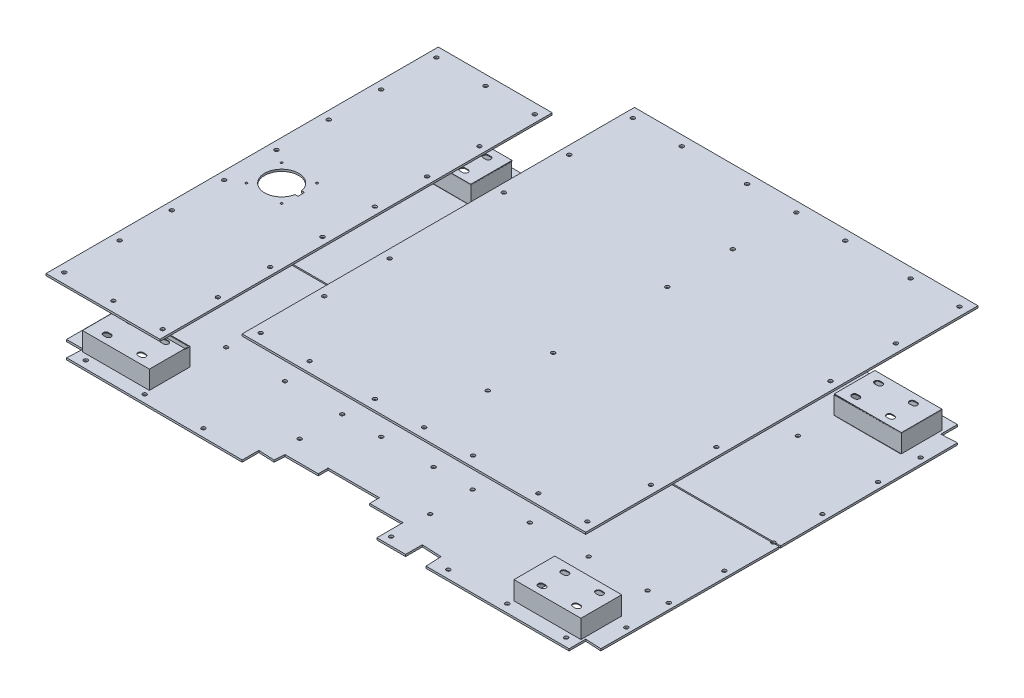
SolidWorks part; units mm, degrees
ref_plane "Front Plane" through (0, 0, 0) normal (0, 0, 1) x (1, 0, 0)
ref_plane "Top Plane" through (0, 0, 0) normal (0, 1, 0) x (1, 0, 0)
ref_plane "Right Plane" through (0, 0, 0) normal (1, 0, 0) x (0, 0, -1)
sketch "Sketch2" plane through (0, 422.0595, 0) normal (0, 1, 0) x (1, 0, 0)
  line L1 (715.0951, -383.2952) -> (690.8951, -384.4952)
  line L2 (690.8951, -384.4952) -> (690.8951, -359.0952)
  line L3 (690.8951, -359.0952) -> (466.2951, -359.0952)
  line L4 (466.2951, -359.0952) -> (465.0951, -383.2952)
  line L5 (465.0951, -383.2952) -> (440.8951, -384.4952)
  line L6 (440.8951, -384.4952) -> (440.8951, -359.0952)
  line L7 (440.8951, -359.0952) -> (390.8951, -359.0952)
  line L8 (390.8951, -359.0952) -> (390.8951, -399.0952)
  line L9 (390.8951, -483.6952) -> (390.8951, -359.0952) construction
  line L10 (390.8951, -399.0952) -> (216.2951, -399.0952)
  line L11 (216.2951, -384.4952) -> (216.2951, -483.6952) construction
  line L12 (216.2951, -399.0952) -> (215.0951, -383.2952)
  line L13 (215.0951, -383.2952) -> (190.8951, -384.4952)
  line L14 (190.8951, -384.4952) -> (190.8951, -359.0952)
  line L15 (190.8951, -359.0952) -> (-84.9049, -360.2952)
  line L16 (-84.9049, -360.2952) -> (-83.7049, -384.4952)
  line L17 (-83.7049, -384.4952) -> (-109.1049, -384.4952)
  line L18 (-109.1049, -384.4952) -> (-109.1049, -933.6952)
  line L19 (-109.1049, -933.6952) -> (-109.1049, -384.4952) construction
  line L20 (715.0951, -383.2952) -> (716.2951, -659.0952)
  line L21 (716.2951, -384.4952) -> (716.2951, -933.6952) construction
  line L22 (716.2951, -659.0952) -> (-109.1049, -659.0952) construction
  line L23 (715.0951, -934.8952) -> (716.2951, -659.0952)
  line L24 (-83.7049, -933.6952) -> (-109.1049, -933.6952)
  line L25 (-84.9049, -957.8952) -> (-83.7049, -933.6952)
  line L26 (190.8951, -959.0952) -> (-84.9049, -957.8952)
  line L27 (190.8951, -933.6952) -> (190.8951, -959.0952)
  line L28 (215.0951, -934.8952) -> (190.8951, -933.6952)
  line L29 (216.2951, -919.0952) -> (215.0951, -934.8952)
  line L30 (390.8951, -919.0952) -> (216.2951, -919.0952)
  line L31 (390.8951, -959.0952) -> (390.8951, -919.0952)
  line L32 (440.8951, -959.0952) -> (390.8951, -959.0952)
  line L33 (440.8951, -933.6952) -> (440.8951, -959.0952)
  line L34 (465.0951, -934.8952) -> (440.8951, -933.6952)
  line L35 (466.2951, -959.0952) -> (465.0951, -934.8952)
  line L36 (690.8951, -959.0952) -> (466.2951, -959.0952)
  line L37 (690.8951, -933.6952) -> (690.8951, -959.0952)
  line L38 (715.0951, -934.8952) -> (690.8951, -933.6952)
  line L39 (712.1088, -386.4469) -> (713.2907, -658.0952)
  line L40 (712.1088, -386.4469) -> (687.8951, -387.6476)
  line L41 (687.8951, -387.6476) -> (687.8951, -362.0952)
  line L42 (687.8951, -362.0952) -> (469.15, -362.0952)
  line L43 (469.15, -362.0952) -> (467.9569, -386.1569)
  line L44 (467.9569, -386.1569) -> (437.8951, -387.6476)
  line L45 (437.8951, -387.6476) -> (437.8951, -362.0952)
  line L46 (437.8951, -362.0952) -> (393.8951, -362.0952)
  line L47 (393.8951, -362.0952) -> (393.8951, -402.0952)
  line L48 (393.8951, -402.0952) -> (213.5143, -402.0952)
  line L49 (213.5143, -402.0952) -> (212.325, -386.4362)
  line L50 (212.325, -386.4362) -> (187.8951, -387.6476)
  line L51 (187.8951, -387.6476) -> (187.8951, -362.1082)
  line L52 (187.8951, -362.1082) -> (-81.7531, -363.2815)
  line L53 (-81.7531, -363.2815) -> (-80.5525, -387.4952)
  line L54 (-80.5525, -387.4952) -> (-106.1049, -387.4952)
  line L55 (-106.1049, -387.4952) -> (-106.1049, -658.0952)
  line L56 (-80.5525, -930.6952) -> (-106.1049, -930.6952)
  line L57 (-81.7531, -954.9089) -> (-80.5525, -930.6952)
  line L58 (187.8951, -956.0821) -> (-81.7531, -954.9089)
  line L59 (187.8951, -930.5427) -> (187.8951, -956.0821)
  line L60 (212.325, -931.7541) -> (187.8951, -930.5427)
  line L61 (213.5143, -916.0952) -> (212.325, -931.7541)
  line L62 (393.8951, -916.0952) -> (213.5143, -916.0952)
  line L63 (393.8951, -956.0952) -> (393.8951, -916.0952)
  line L64 (437.8951, -956.0952) -> (393.8951, -956.0952)
  line L65 (437.8951, -930.5427) -> (437.8951, -956.0952)
  line L66 (467.9569, -932.0334) -> (437.8951, -930.5427)
  line L67 (469.15, -956.0952) -> (467.9569, -932.0334)
  line L68 (687.8951, -956.0952) -> (469.15, -956.0952)
  line L69 (687.8951, -930.5427) -> (687.8951, -956.0952)
  line L70 (712.1088, -931.7434) -> (687.8951, -930.5427)
  line L71 (712.1088, -931.7434) -> (713.2907, -660.0952)
  line L72 (716.2951, -658.0952) -> (716.2907, -658.0952)
  line L73 (716.2951, -660.0952) -> (716.2907, -660.0952)
  line L74 (713.2907, -660.0952) -> (-106.1049, -660.0952)
  line L75 (713.2907, -658.0952) -> (-106.1049, -658.0952)
  line L76 (716.2951, -660.0952) -> (-109.1049, -660.0952) construction
  line L77 (-106.1049, -660.0952) -> (-106.1049, -930.6952)
  line L78 (716.2951, -658.0952) -> (-109.1049, -658.0952) construction
  line L80 (-106.1049, -387.4952) -> (-106.1049, -930.6952) construction
  line L81 (712.1088, -386.4469) -> (713.2951, -659.0952) construction
  line L82 (712.1088, -931.7434) -> (713.2951, -659.0952) construction
  circle A0 centre (-96.2049, -884.0952) radius 3 construction
  circle A1 centre (116.2951, -819.0952) radius 3 construction
  circle A2 centre (-63.7049, -819.0952) radius 3 construction
  circle A3 centre (-96.2049, -819.0952) radius 3 construction
  circle A4 centre (-96.2049, -884.0952) radius 3
  circle A5 centre (116.2951, -819.0952) radius 3
  circle A6 centre (-63.7049, -819.0952) radius 3
  circle A7 centre (-96.2049, -819.0952) radius 3
  circle A8 centre (-96.2049, -734.0952) radius 3 construction
  circle A9 centre (-96.2049, -734.0952) radius 3
  circle A10 centre (116.2951, -943.6952) radius 3 construction
  circle A11 centre (26.2951, -943.6952) radius 3 construction
  circle A12 centre (-63.7049, -943.6952) radius 3 construction
  circle A13 centre (116.2951, -943.6952) radius 3
  circle A14 centre (26.2951, -943.6952) radius 3
  circle A15 centre (-63.7049, -943.6952) radius 3
  circle A16 centre (-96.2049, -659.0952) radius 3 construction
  circle A17 centre (-96.2049, -659.0952) radius 3
  circle A18 centre (26.2951, -819.0952) radius 3 construction
  circle A19 centre (26.2951, -819.0952) radius 3
  circle A20 centre (343.5951, -819.0952) radius 3 construction
  circle A21 centre (203.7951, -734.0952) radius 3 construction
  circle A22 centre (263.5951, -819.0952) radius 3 construction
  circle A23 centre (203.7951, -819.0952) radius 3 construction
  circle A24 centre (203.7951, -884.0952) radius 3 construction
  circle A25 centre (343.5951, -819.0952) radius 3
  circle A26 centre (203.7951, -734.0952) radius 3
  circle A27 centre (263.5951, -819.0952) radius 3
  circle A28 centre (203.7951, -819.0952) radius 3
  circle A29 centre (203.7951, -884.0952) radius 3
  circle A30 centre (203.7951, -659.0952) radius 3 construction
  circle A31 centre (203.7951, -659.0952) radius 3
  circle A32 centre (26.2951, -499.0952) radius 3 construction
  circle A33 centre (26.2951, -499.0952) radius 3
  circle A34 centre (116.2951, -499.0952) radius 3 construction
  circle A35 centre (116.2951, -499.0952) radius 3
  circle A36 centre (203.7951, -499.0952) radius 3 construction
  circle A37 centre (203.7951, -499.0952) radius 3
  circle A38 centre (203.7951, -434.0952) radius 3 construction
  circle A39 centre (203.7951, -434.0952) radius 3
  circle A40 centre (116.2951, -374.4952) radius 3 construction
  circle A41 centre (116.2951, -374.4952) radius 3
  circle A42 centre (26.2951, -374.4952) radius 3 construction
  circle A43 centre (26.2951, -374.4952) radius 3
  circle A44 centre (-63.7049, -374.4952) radius 3 construction
  circle A45 centre (-63.7049, -374.4952) radius 3
  circle A46 centre (-96.2049, -434.0952) radius 3 construction
  circle A47 centre (-96.2049, -499.0952) radius 3 construction
  circle A48 centre (-96.2049, -584.0952) radius 3 construction
  circle A49 centre (-96.2049, -434.0952) radius 3
  circle A50 centre (-96.2049, -499.0952) radius 3
  circle A51 centre (-96.2049, -584.0952) radius 3
  circle A52 centre (-63.7049, -499.0952) radius 3 construction
  circle A53 centre (-63.7049, -499.0952) radius 3
  circle A54 centre (203.7951, -584.0952) radius 3 construction
  circle A55 centre (203.7951, -584.0952) radius 3
  circle A56 centre (403.3951, -584.0952) radius 3 construction
  circle A57 centre (403.3951, -584.0952) radius 3
  circle A58 centre (490.8951, -499.0952) radius 3 construction
  circle A59 centre (490.8951, -499.0952) radius 3
  circle A60 centre (580.8951, -499.0952) radius 3 construction
  circle A61 centre (580.8951, -499.0952) radius 3
  circle A62 centre (490.8951, -374.4952) radius 3 construction
  circle A63 centre (490.8951, -374.4952) radius 3
  circle A64 centre (580.8951, -374.4952) radius 3 construction
  circle A65 centre (580.8951, -374.4952) radius 3
  circle A66 centre (703.3951, -584.0952) radius 3 construction
  circle A67 centre (703.3951, -499.0952) radius 3 construction
  circle A68 centre (703.3951, -434.0952) radius 3 construction
  circle A69 centre (670.8951, -374.4952) radius 3 construction
  circle A70 centre (703.3951, -584.0952) radius 3
  circle A71 centre (703.3951, -499.0952) radius 3
  circle A72 centre (703.3951, -434.0952) radius 3
  circle A73 centre (670.8951, -374.4952) radius 3
  circle A74 centre (703.3951, -884.0952) radius 3 construction
  circle A75 centre (703.3951, -819.0952) radius 3 construction
  circle A76 centre (703.3951, -734.0952) radius 3 construction
  circle A77 centre (703.3951, -659.0952) radius 3 construction
  circle A78 centre (703.3951, -884.0952) radius 3
  circle A79 centre (703.3951, -819.0952) radius 3
  circle A80 centre (703.3951, -734.0952) radius 3
  circle A81 centre (703.3951, -659.0952) radius 3
  circle A82 centre (490.8951, -943.6952) radius 3 construction
  circle A83 centre (580.8951, -943.6952) radius 3 construction
  circle A84 centre (670.8951, -943.6952) radius 3 construction
  circle A85 centre (490.8951, -943.6952) radius 3
  circle A86 centre (580.8951, -943.6952) radius 3
  circle A87 centre (670.8951, -943.6952) radius 3
  circle A89 centre (580.8951, -819.0952) radius 3 construction
  circle A90 centre (670.8951, -819.0952) radius 3 construction
  circle A91 centre (580.8951, -819.0952) radius 3
  circle A92 centre (670.8951, -819.0952) radius 3
  circle A93 centre (490.8951, -819.0952) radius 3 construction
  circle A94 centre (490.8951, -819.0952) radius 3
  circle A95 centre (403.3951, -943.6952) radius 3 construction
  circle A96 centre (403.3951, -884.0952) radius 3 construction
  circle A97 centre (403.3951, -819.0952) radius 3 construction
  circle A98 centre (403.3951, -734.0952) radius 3 construction
  circle A99 centre (403.3951, -943.6952) radius 3
  circle A100 centre (403.3951, -884.0952) radius 3
  circle A101 centre (403.3951, -819.0952) radius 3
  circle A102 centre (403.3951, -734.0952) radius 3
  circle A103 centre (403.3951, -659.0952) radius 3 construction
  circle A104 centre (403.3951, -499.0952) radius 3 construction
  circle A105 centre (403.3951, -434.0952) radius 3 construction
  circle A106 centre (403.3951, -374.4952) radius 3 construction
  circle A107 centre (403.3951, -659.0952) radius 3
  circle A108 centre (403.3951, -499.0952) radius 3
  circle A109 centre (403.3951, -434.0952) radius 3
  circle A110 centre (403.3951, -374.4952) radius 3
  circle A111 centre (343.5951, -499.0952) radius 3 construction
  circle A113 centre (263.5951, -499.0952) radius 3 construction
  circle A114 centre (343.5951, -499.0952) radius 3
  circle A115 centre (263.5951, -499.0952) radius 3
  dimension "D1" = 40
  dimension "D2" = 3
  dimension "D3" = 1
  dimension "D4" = 1
extrude "Boss-Extrude1" add sketch "Sketch2" along normal blind 3 contours A107 L75 A81 L39 L40 L41 L42 L43 L44 L45 L46 L47 L48 L49 L50 L51 L52 L53 L54 L55 A17 A31 A115 A114 A110 A109 A108 A73 A72 A71 A70 A65 A63 A61 | A107 L74 A31 A17 L77 L56 L57 L58 L59 L60 L61 L62 L63 L64 L65 L66 L67 L68 L69 L70 L71 A81 A102 A101 A100 A99 A94 A92 A91 A87 A86 A85 A80 A79 region at (303.342, 422.0595, 515.8841) region at (303.2971, 422.0595, 802.3042)
sketch "Sketch4" plane through (0, 592.0595, 0) normal (0, 1, 0) x (1, 0, 0)
  line L0 (716.2951, -359.0952) -> (190.8951, -359.0952) construction
  line L1 (190.8951, -359.0952) -> (190.8951, -959.0952) construction
  line L2 (190.8951, -933.6952) -> (190.8951, -384.4952) construction
  line L3 (716.2951, -959.0952) -> (716.2951, -359.0952) construction
  line L4 (190.8951, -959.0952) -> (716.2951, -959.0952) construction
  line L5 (716.2951, -359.0952) -> (190.8951, -359.0952)
  line L6 (190.8951, -359.0952) -> (190.8951, -959.0952)
  line L7 (190.8951, -933.6952) -> (190.8951, -384.4952)
  line L8 (716.2951, -959.0952) -> (716.2951, -359.0952)
  line L9 (190.8951, -959.0952) -> (716.2951, -959.0952)
  line L10 (190.8951, -359.0952) -> (716.2951, -959.0952) construction
  line L11 (190.8951, -959.0952) -> (716.2951, -359.0952) construction
  line L12 (453.5951, -659.0952) -> (716.2951, -659.0952) construction
  circle A1 centre (628.5951, -943.6952) radius 3 construction
  circle A2 centre (703.3951, -943.6952) radius 3 construction
  circle A3 centre (528.5951, -943.6952) radius 3 construction
  circle A4 centre (703.3951, -846.3952) radius 3 construction
  circle A5 centre (703.3951, -746.3952) radius 3 construction
  circle A6 centre (453.7951, -943.6952) radius 3 construction
  circle A7 centre (453.7951, -846.3952) radius 3 construction
  circle A8 centre (378.5951, -943.6952) radius 3 construction
  circle A9 centre (278.5951, -943.6952) radius 3 construction
  circle A10 centre (203.7951, -943.6952) radius 3 construction
  circle A11 centre (203.7951, -746.3952) radius 3 construction
  circle A12 centre (203.7951, -846.3952) radius 3 construction
  circle A13 centre (453.7951, -746.3952) radius 3 construction
  circle A14 centre (453.7951, -746.3952) radius 3
  circle A15 centre (203.7951, -846.3952) radius 3
  circle A16 centre (203.7951, -746.3952) radius 3
  circle A17 centre (203.7951, -943.6952) radius 3
  circle A18 centre (278.5951, -943.6952) radius 3
  circle A19 centre (378.5951, -943.6952) radius 3
  circle A20 centre (453.7951, -846.3952) radius 3
  circle A21 centre (453.7951, -943.6952) radius 3
  circle A22 centre (703.3951, -746.3952) radius 3
  circle A23 centre (703.3951, -846.3952) radius 3
  circle A24 centre (528.5951, -943.6952) radius 3
  circle A25 centre (703.3951, -943.6952) radius 3
  circle A26 centre (628.5951, -943.6952) radius 3
  circle A40 centre (628.5951, -374.4952) radius 3
  circle A41 centre (703.3951, -374.4952) radius 3
  circle A42 centre (528.5951, -374.4952) radius 3
  circle A43 centre (703.3951, -471.7952) radius 3
  circle A44 centre (703.3951, -571.7952) radius 3
  circle A45 centre (453.7951, -374.4952) radius 3
  circle A46 centre (453.7951, -471.7952) radius 3
  circle A47 centre (378.5951, -374.4952) radius 3
  circle A48 centre (278.5951, -374.4952) radius 3
  circle A49 centre (203.7951, -374.4952) radius 3
  circle A50 centre (203.7951, -571.7952) radius 3
  circle A51 centre (203.7951, -471.7952) radius 3
  circle A52 centre (453.7951, -571.7952) radius 3
extrude "Boss-Extrude2" add sketch "Sketch4" along normal blind 3 separate body contours L5 L6 L9 L8 | A49 | A48 | A47 | A46 | A51 | A50 | A52 | A45 | A42 | A40 | A41 | A43 | A44 | A22 | A14 | A16 | A15 | A18 | A19 | A20 | A21 | A24 | A26 | A23 | A25 | A17
sketch "Sketch6" plane through (0, 522.0595, 0) normal (0, 1, 0) x (1, 0, 0)
  line L0 (-109.1049, -959.0952) -> (-109.1049, -359.0952) construction
  line L1 (65.0951, -384.4952) -> (65.0951, -933.6952) construction
  line L2 (-109.1049, -959.0952) -> (-109.1049, -359.0952)
  line L3 (65.0951, -384.4952) -> (65.0951, -933.6952)
  line L4 (65.0951, -933.6952) -> (65.0951, -959.0952)
  line L5 (190.8951, -959.0952) -> (-109.1049, -959.0952) construction
  line L6 (65.0951, -959.0952) -> (-109.1049, -959.0952)
  line L7 (65.0951, -384.4952) -> (65.0951, -359.0952)
  line L8 (190.8951, -359.0952) -> (-109.1049, -359.0952) construction
  line L9 (65.0951, -359.0952) -> (-109.1049, -359.0952)
  line L10 (65.0951, -659.0952) -> (-109.1049, -659.0952) construction
  circle A0 centre (-96.6049, -943.6952) radius 3 construction
  circle A1 centre (-21.3999, -943.6952) radius 3 construction
  circle A2 centre (53.7951, -943.6952) radius 3 construction
  circle A3 centre (-96.6049, -943.6952) radius 3
  circle A4 centre (-21.3999, -943.6952) radius 3
  circle A5 centre (53.7951, -943.6952) radius 3
  circle A6 centre (-96.6049, -859.0952) radius 3 construction
  circle A7 centre (53.7951, -859.0952) radius 3 construction
  circle A8 centre (-96.6049, -859.0952) radius 3
  circle A9 centre (53.7951, -859.0952) radius 3
  circle A10 centre (53.7951, -699.0952) radius 3 construction
  circle A11 centre (-96.6049, -699.0952) radius 3 construction
  circle A12 centre (53.7951, -779.0952) radius 3 construction
  circle A13 centre (-96.6049, -779.0952) radius 3 construction
  circle A14 centre (53.7951, -699.0952) radius 3
  circle A15 centre (-96.6049, -699.0952) radius 3
  circle A16 centre (53.7951, -779.0952) radius 3
  circle A17 centre (-96.6049, -779.0952) radius 3
  circle A27 centre (-96.6049, -619.0952) radius 3
  circle A28 centre (-96.6049, -539.0952) radius 3
  circle A29 centre (53.7951, -539.0952) radius 3
  circle A30 centre (53.7951, -619.0952) radius 3
  circle A31 centre (53.7951, -459.0952) radius 3
  circle A32 centre (-96.6049, -459.0952) radius 3
  circle A33 centre (53.7951, -374.4952) radius 3
  circle A34 centre (-21.3999, -374.4952) radius 3
  circle A35 centre (-96.6049, -374.4952) radius 3
extrude "Boss-Extrude3" add sketch "Sketch6" along normal blind 3 separate body
sketch "Sketch9" plane through (0, 525.0595, 0) normal (0, 1, 0) x (1, 0, 0)
  line L0 (-48.7049, -659.0952) -> (-22.7049, -659.0952) construction
  line L1 (-48.7049, -654.0952) -> (-22.7049, -654.0952) construction
  line L2 (-48.7049, -664.0952) -> (-22.7049, -664.0952) construction
  line L3 (-23.1902, -654.0952) -> (-18.6902, -654.0952)
  line L4 (-18.6902, -654.0952) -> (-18.6902, -664.0952)
  line L5 (-18.6902, -664.0952) -> (-23.1902, -664.0952)
  arc A0 (-23.1902, -654.0952) -> (-23.1902, -664.0952) centre (-48.7049, -659.0952) ccw
  dimension "D1" = 52
  dimension "D4" = 4.5
  dimension "D2" = 5
  dimension "D3" = 5
extrude "Cut-Extrude1" cut sketch "Sketch9" against normal up to next (3 mm away)
sketch "Sketch10" plane through (0, 525.0595, 0) normal (0, 1, 0) x (1, 0, 0)
  circle A0 centre (-21.7049, -632.0952) radius 1.6
  circle A1 centre (-21.7049, -686.0952) radius 1.6
  circle A2 centre (-75.7049, -632.0952) radius 1.6
  circle A3 centre (-75.7049, -686.0952) radius 1.6
  dimension "D1" = 3.2
  dimension "D2" = 3.2
  dimension "D3" = 3.2
  dimension "D4" = 3.2
extrude "Cut-Extrude4" cut sketch "Sketch10" against normal up to next (3 mm away)
sketch "Sketch11" plane through (0, 422.0595, 0) normal (0, -1, 0) x (1, 0, 0)
  line L0 (264.2951, 916.0952) -> (264.2951, 901.0952)
  line L1 (393.8951, 916.0952) -> (213.5143, 916.0952) construction
  line L2 (264.2951, 901.0952) -> (342.8951, 901.0952)
  line L3 (342.8951, 901.0952) -> (342.8951, 916.0952)
  line L4 (264.2951, 402.0952) -> (342.8951, 402.0952)
  line L5 (390.8951, 959.0952) -> (390.8951, 834.4952) construction
  line L6 (216.2951, 959.0952) -> (216.2951, 834.4952) construction
  line L7 (216.2951, 659.0952) -> (416.2951, 659.0952) construction
  line L8 (216.2951, 809.0952) -> (216.2951, 509.0952) construction
  line L9 (416.2951, 809.0952) -> (416.2951, 509.0952) construction
  line L10 (342.8951, 417.0952) -> (342.8951, 402.0952)
  line L11 (264.2951, 417.0952) -> (342.8951, 417.0952)
  line L12 (264.2951, 402.0952) -> (264.2951, 417.0952)
  line L13 (264.2951, 916.0952) -> (342.8951, 916.0952)
  dimension "D1" = 15
  dimension "D2" = 48
  dimension "D3" = 48
extrude "Cut-Extrude5" cut sketch "Sketch11" against normal up to next (3 mm away)
sketch "Sketch13" plane through (0, 422.0595, 0) normal (0, -1, 0) x (1, 0, 0)
  line L1 (683.5951, 933.6952) -> (583.5951, 933.6952)
  line L3 (683.5951, 873.6952) -> (583.5951, 873.6952)
  line L4 (583.5951, 933.6952) -> (583.5951, 873.6952)
  line L7 (303.5951, 901.0952) -> (303.5951, 417.0952) construction
  line L22 (683.5951, 933.6952) -> (683.5951, 873.6952)
  line L24 (264.2951, 901.0952) -> (342.8951, 901.0952) construction
  line L25 (342.8951, 417.0952) -> (264.2951, 417.0952) construction
  line L26 (303.5951, 659.0952) -> (712.9729, 659.0952) construction
  line L29 (687.8951, 956.0952) -> (469.15, 956.0952) construction
  line L30 (683.5951, 384.4952) -> (683.5951, 444.4952)
  line L31 (583.5951, 384.4952) -> (583.5951, 444.4952)
  line L32 (683.5951, 444.4952) -> (583.5951, 444.4952)
  line L33 (683.5951, 384.4952) -> (583.5951, 384.4952)
  line L34 (-76.4049, 933.6952) -> (-76.4049, 873.6952)
  line L35 (23.5951, 933.6952) -> (23.5951, 873.6952)
  line L36 (-76.4049, 873.6952) -> (23.5951, 873.6952)
  line L37 (-76.4049, 933.6952) -> (23.5951, 933.6952)
  line L38 (-76.4049, 384.4952) -> (23.5951, 384.4952)
  line L39 (-76.4049, 444.4952) -> (23.5951, 444.4952)
  line L40 (23.5951, 384.4952) -> (23.5951, 444.4952)
  line L41 (-76.4049, 384.4952) -> (-76.4049, 444.4952)
  dimension "D1" = 60
  dimension "D2" = 100
  dimension "D3" = 22.4
  dimension "D4" = 380
extrude "Cut-Extrude6" cut sketch "Sketch13" against normal up to next (3 mm away)
sketch "Sketch15" plane through (0, 422.0595, 0) normal (0, -1, 0) x (1, 0, 0)
  line L0 (583.5951, 933.6952) -> (583.5951, 873.6952) construction
  line L1 (583.5951, 873.6952) -> (683.5951, 873.6952) construction
  line L2 (683.5951, 933.6952) -> (583.5951, 933.6952) construction
  line L3 (683.5951, 873.6952) -> (683.5951, 933.6952) construction
  line L4 (583.5951, 933.6952) -> (583.5951, 873.6952)
  line L5 (583.5951, 873.6952) -> (683.5951, 873.6952)
  line L6 (683.5951, 933.6952) -> (583.5951, 933.6952)
  line L7 (683.5951, 873.6952) -> (683.5951, 933.6952)
  line L8 (582.3951, 934.8952) -> (582.3951, 872.4952)
  line L9 (582.3951, 872.4952) -> (684.7951, 872.4952)
  line L10 (684.7951, 872.4952) -> (684.7951, 934.8952)
  line L11 (684.7951, 934.8952) -> (582.3951, 934.8952)
  line L13 (303.5951, 901.0952) -> (303.5951, 416.7343) construction
  line L14 (264.2951, 901.0952) -> (342.8951, 901.0952) construction
  line L15 (303.5951, 658.9147) -> (713.2907, 658.0952) construction
  line L16 (683.6879, 381.4114) -> (581.2887, 381.8211)
  line L17 (683.9375, 443.8109) -> (683.6879, 381.4114)
  line L18 (581.5384, 444.2206) -> (683.9375, 443.8109)
  line L19 (581.2887, 381.8211) -> (581.5384, 444.2206)
  line L20 (682.7327, 442.6157) -> (682.4927, 382.6162)
  line L21 (682.4927, 382.6162) -> (582.4935, 383.0163)
  line L22 (582.7335, 443.0158) -> (682.7327, 442.6157)
  line L23 (582.4935, 383.0163) -> (582.7335, 443.0158)
  line L24 (24.6967, 383.0163) -> (24.4566, 443.0158)
  line L25 (24.4566, 443.0158) -> (-75.5426, 442.6157)
  line L26 (-75.3025, 382.6162) -> (24.6967, 383.0163)
  line L27 (-75.5426, 442.6157) -> (-75.3025, 382.6162)
  line L28 (25.9015, 381.8211) -> (25.6518, 444.2206)
  line L29 (25.6518, 444.2206) -> (-76.7474, 443.8109)
  line L30 (-76.7474, 443.8109) -> (-76.4977, 381.4114)
  line L31 (-76.4977, 381.4114) -> (25.9015, 381.8211)
  line L32 (-77.6049, 934.8952) -> (24.7951, 934.8952)
  line L33 (-77.6049, 872.4952) -> (-77.6049, 934.8952)
  line L34 (24.7951, 872.4952) -> (-77.6049, 872.4952)
  line L35 (24.7951, 934.8952) -> (24.7951, 872.4952)
  line L36 (-76.4049, 873.6952) -> (-76.4049, 933.6952)
  line L37 (-76.4049, 933.6952) -> (23.5951, 933.6952)
  line L38 (23.5951, 873.6952) -> (-76.4049, 873.6952)
  line L39 (23.5951, 933.6952) -> (23.5951, 873.6952)
  dimension "D1" = 1.2
extrude "Boss-Extrude4" add sketch "Sketch15" against normal blind 27 from surface starting at face at (633.5951, 425.0595, 414.4952)
sketch "Sketch16" plane through (0, 452.0595, 0) normal (0, 1, 0) x (-1, 0, 0)
  line L0 (-684.7951, 934.8952) -> (-582.3951, 934.8952) construction
  line L1 (-684.7951, 934.8952) -> (-582.3951, 934.8952)
  line L2 (-684.7951, 934.8952) -> (-684.7951, 872.4952)
  line L3 (-684.7951, 872.4952) -> (-582.3951, 872.4952)
  line L4 (-582.3951, 934.8952) -> (-582.3951, 872.4952)
  line L5 (-684.7951, 872.4952) -> (-684.7951, 934.8952) construction
  line L6 (-582.3951, 934.8952) -> (-582.3951, 872.4952) construction
  line L7 (-582.3951, 872.4952) -> (-684.7951, 872.4952) construction
  line L8 (-581.5384, 444.2206) -> (-581.2887, 381.8211) construction
  line L9 (-683.9375, 443.8109) -> (-581.2887, 443.8109)
  line L10 (-683.9375, 443.8109) -> (-683.9375, 381.8211)
  line L11 (-683.9375, 381.8211) -> (-581.2887, 381.8211)
  line L12 (-581.2887, 443.8109) -> (-581.2887, 381.8211)
  line L13 (-581.2887, 381.8211) -> (-683.6879, 381.4114) construction
  line L14 (77.6049, 934.8952) -> (77.6049, 872.4952) construction
  line L15 (-24.7951, 934.8952) -> (77.6049, 934.8952)
  line L16 (-24.7951, 934.8952) -> (-24.7951, 880.4952)
  line L17 (-24.7951, 880.4952) -> (77.6049, 880.4952)
  line L18 (77.6049, 934.8952) -> (77.6049, 880.4952)
  line L19 (76.7474, 443.8109) -> (76.4977, 381.4114) construction
  line L20 (-25.6518, 444.2206) -> (76.4964, 444.2206)
  line L21 (-25.6518, 444.2206) -> (-25.6518, 381.0889)
  line L22 (-25.6518, 381.0889) -> (76.4964, 381.0889)
  line L23 (76.4964, 444.2206) -> (76.4964, 381.0889)
extrude "Boss-Extrude5" add sketch "Sketch16" along normal blind 1.2
sketch "Sketch18" plane through (0, 453.2595, 0) normal (0, 1, 0) x (1, 0, 0)
  line L0 (656.0609, -399.7221) -> (652.0609, -399.7381) construction
  line L1 (652.0289, -391.7381) -> (656.0289, -391.7221) construction
  line L2 (603.0293, -391.9342) -> (599.0294, -391.9502) construction
  line L3 (599.0614, -399.9501) -> (603.0613, -399.9341) construction
  line L4 (652.169, -426.7379) -> (656.1689, -426.7219) construction
  line L5 (656.2009, -434.7218) -> (652.201, -434.7378) construction
  line L6 (599.2014, -434.9498) -> (603.2014, -434.9338) construction
  line L7 (603.1694, -426.9339) -> (599.1694, -426.9499) construction
  line L8 (656.0609, -399.7221) -> (652.0609, -399.7381)
  line L9 (652.0289, -391.7381) -> (656.0289, -391.7221)
  line L10 (603.0293, -391.9342) -> (599.0294, -391.9502)
  line L11 (599.0614, -399.9501) -> (603.0613, -399.9341)
  line L12 (652.169, -426.7379) -> (656.1689, -426.7219)
  line L13 (656.2009, -434.7218) -> (652.201, -434.7378)
  line L14 (599.2014, -434.9498) -> (603.2014, -434.9338)
  line L15 (603.1694, -426.9339) -> (599.1694, -426.9499)
  arc A0 (652.0289, -391.7381) -> (652.0609, -399.7381) centre (652.0449, -395.7381) ccw construction
  arc A1 (656.0609, -399.7221) -> (656.0289, -391.7221) centre (656.0449, -395.7221) ccw construction
  arc A2 (603.0613, -399.9341) -> (603.0293, -391.9342) centre (603.0453, -395.9341) ccw construction
  arc A3 (599.0294, -391.9502) -> (599.0614, -399.9501) centre (599.0454, -395.9501) ccw construction
  arc A4 (652.169, -426.7379) -> (652.201, -434.7378) centre (652.185, -430.7378) ccw construction
  arc A5 (656.2009, -434.7218) -> (656.1689, -426.7219) centre (656.1849, -430.7218) ccw construction
  arc A6 (599.1694, -426.9499) -> (599.2014, -434.9498) centre (599.1854, -430.9499) ccw construction
  arc A7 (603.2014, -434.9338) -> (603.1694, -426.9339) centre (603.1854, -430.9339) ccw construction
  arc A8 (652.0289, -391.7381) -> (652.0609, -399.7381) centre (652.0449, -395.7381) ccw
  arc A9 (656.0609, -399.7221) -> (656.0289, -391.7221) centre (656.0449, -395.7221) ccw
  arc A10 (603.0613, -399.9341) -> (603.0293, -391.9342) centre (603.0453, -395.9341) ccw
  arc A11 (599.0294, -391.9502) -> (599.0614, -399.9501) centre (599.0454, -395.9501) ccw
  arc A12 (652.169, -426.7379) -> (652.201, -434.7378) centre (652.185, -430.7378) ccw
  arc A13 (656.2009, -434.7218) -> (656.1689, -426.7219) centre (656.1849, -430.7218) ccw
  arc A14 (599.1694, -426.9499) -> (599.2014, -434.9498) centre (599.1854, -430.9499) ccw
  arc A15 (603.2014, -434.9338) -> (603.1694, -426.9339) centre (603.1854, -430.9339) ccw
extrude "Cut-Extrude7" cut sketch "Sketch18" against normal through all
sketch "Sketch19" plane through (0, 453.2595, 0) normal (0, 1, 0) x (1, 0, 0)
  line L19 (614.0951, -882.6952) -> (610.0951, -882.6952) construction
  line L20 (610.0951, -890.6952) -> (614.0951, -890.6952) construction
  line L21 (663.0951, -882.6952) -> (667.0951, -882.6952) construction
  line L22 (667.0951, -890.6952) -> (663.0951, -890.6952) construction
  line L23 (614.0951, -917.6952) -> (610.0951, -917.6952) construction
  line L24 (610.0951, -925.6952) -> (614.0951, -925.6952) construction
  line L25 (663.0951, -917.6952) -> (667.0951, -917.6952) construction
  line L26 (667.0951, -925.6952) -> (663.0951, -925.6952) construction
  line L27 (614.0951, -882.6952) -> (610.0951, -882.6952)
  line L28 (610.0951, -890.6952) -> (614.0951, -890.6952)
  line L29 (663.0951, -882.6952) -> (667.0951, -882.6952)
  line L30 (667.0951, -890.6952) -> (663.0951, -890.6952)
  line L31 (614.0951, -917.6952) -> (610.0951, -917.6952)
  line L32 (610.0951, -925.6952) -> (614.0951, -925.6952)
  line L33 (663.0951, -917.6952) -> (667.0951, -917.6952)
  line L34 (667.0951, -925.6952) -> (663.0951, -925.6952)
  arc A19 (610.0951, -882.6952) -> (610.0951, -890.6952) centre (610.0951, -886.6952) ccw construction
  arc A20 (614.0951, -890.6952) -> (614.0951, -882.6952) centre (614.0951, -886.6952) ccw construction
  arc A21 (663.0951, -882.6952) -> (663.0951, -890.6952) centre (663.0951, -886.6952) ccw construction
  arc A22 (667.0951, -890.6952) -> (667.0951, -882.6952) centre (667.0951, -886.6952) ccw construction
  arc A23 (614.0951, -925.6952) -> (614.0951, -917.6952) centre (614.0951, -921.6952) ccw construction
  arc A24 (610.0951, -917.6952) -> (610.0951, -925.6952) centre (610.0951, -921.6952) ccw construction
  arc A25 (663.0951, -917.6952) -> (663.0951, -925.6952) centre (663.0951, -921.6952) ccw construction
  arc A26 (667.0951, -925.6952) -> (667.0951, -917.6952) centre (667.0951, -921.6952) ccw construction
  arc A27 (610.0951, -882.6952) -> (610.0951, -890.6952) centre (610.0951, -886.6952) ccw
  arc A28 (614.0951, -890.6952) -> (614.0951, -882.6952) centre (614.0951, -886.6952) ccw
  arc A29 (663.0951, -882.6952) -> (663.0951, -890.6952) centre (663.0951, -886.6952) ccw
  arc A30 (667.0951, -890.6952) -> (667.0951, -882.6952) centre (667.0951, -886.6952) ccw
  arc A31 (614.0951, -925.6952) -> (614.0951, -917.6952) centre (614.0951, -921.6952) ccw
  arc A32 (610.0951, -917.6952) -> (610.0951, -925.6952) centre (610.0951, -921.6952) ccw
  arc A33 (663.0951, -917.6952) -> (663.0951, -925.6952) centre (663.0951, -921.6952) ccw
  arc A34 (667.0951, -925.6952) -> (667.0951, -917.6952) centre (667.0951, -921.6952) ccw
extrude "Cut-Extrude8" cut sketch "Sketch19" against normal through all
sketch "Sketch21" plane through (0, 453.2595, 0) normal (0, 1, 0) x (1, 0, 0)
  line L0 (-50.9049, -917.6952) -> (-54.9049, -917.6952) construction
  line L1 (-54.9049, -925.6952) -> (-50.9049, -925.6952) construction
  line L2 (-50.9049, -882.6952) -> (-54.9049, -882.6952) construction
  line L3 (-54.9049, -890.6952) -> (-50.9049, -890.6952) construction
  line L4 (-1.9049, -882.6952) -> (2.0951, -882.6952) construction
  line L5 (2.0951, -890.6952) -> (-1.9049, -890.6952) construction
  line L6 (-1.9049, -917.6952) -> (2.0951, -917.6952) construction
  line L7 (2.0951, -925.6952) -> (-1.9049, -925.6952) construction
  line L8 (-50.9049, -917.6952) -> (-54.9049, -917.6952)
  line L9 (-54.9049, -925.6952) -> (-50.9049, -925.6952)
  line L10 (-50.9049, -882.6952) -> (-54.9049, -882.6952)
  line L11 (-54.9049, -890.6952) -> (-50.9049, -890.6952)
  line L12 (-1.9049, -882.6952) -> (2.0951, -882.6952)
  line L13 (2.0951, -890.6952) -> (-1.9049, -890.6952)
  line L14 (-1.9049, -917.6952) -> (2.0951, -917.6952)
  line L15 (2.0951, -925.6952) -> (-1.9049, -925.6952)
  arc A0 (-54.9049, -917.6952) -> (-54.9049, -925.6952) centre (-54.9049, -921.6952) ccw construction
  arc A1 (-50.9049, -925.6952) -> (-50.9049, -917.6952) centre (-50.9049, -921.6952) ccw construction
  arc A2 (-54.9049, -882.6952) -> (-54.9049, -890.6952) centre (-54.9049, -886.6952) ccw construction
  arc A3 (-50.9049, -890.6952) -> (-50.9049, -882.6952) centre (-50.9049, -886.6952) ccw construction
  arc A4 (-1.9049, -882.6952) -> (-1.9049, -890.6952) centre (-1.9049, -886.6952) ccw construction
  arc A5 (2.0951, -890.6952) -> (2.0951, -882.6952) centre (2.0951, -886.6952) ccw construction
  arc A6 (-1.9049, -917.6952) -> (-1.9049, -925.6952) centre (-1.9049, -921.6952) ccw construction
  arc A7 (2.0951, -925.6952) -> (2.0951, -917.6952) centre (2.0951, -921.6952) ccw construction
  arc A8 (-54.9049, -917.6952) -> (-54.9049, -925.6952) centre (-54.9049, -921.6952) ccw
  arc A9 (-50.9049, -925.6952) -> (-50.9049, -917.6952) centre (-50.9049, -921.6952) ccw
  arc A10 (-54.9049, -882.6952) -> (-54.9049, -890.6952) centre (-54.9049, -886.6952) ccw
  arc A11 (-50.9049, -890.6952) -> (-50.9049, -882.6952) centre (-50.9049, -886.6952) ccw
  arc A12 (-1.9049, -882.6952) -> (-1.9049, -890.6952) centre (-1.9049, -886.6952) ccw
  arc A13 (2.0951, -890.6952) -> (2.0951, -882.6952) centre (2.0951, -886.6952) ccw
  arc A14 (-1.9049, -917.6952) -> (-1.9049, -925.6952) centre (-1.9049, -921.6952) ccw
  arc A15 (2.0951, -925.6952) -> (2.0951, -917.6952) centre (2.0951, -921.6952) ccw
extrude "Cut-Extrude9" cut sketch "Sketch21" against normal through all
sketch "Sketch22" plane through (0, 453.2595, 0) normal (0, 1, 0) x (1, 0, 0)
  line L0 (-48.9788, -426.7219) -> (-52.9787, -426.7058) construction
  line L1 (-53.0107, -434.7058) -> (-49.0108, -434.7218) construction
  line L2 (-52.8707, -399.7061) -> (-48.8707, -399.7221) construction
  line L3 (-48.8387, -391.7221) -> (-52.8387, -391.7061) construction
  line L4 (0.0208, -426.9179) -> (4.0208, -426.9339) construction
  line L5 (3.9888, -434.9338) -> (-0.0112, -434.9178) construction
  line L6 (4.1288, -399.9341) -> (0.1289, -399.9181) construction
  line L7 (0.1609, -391.9182) -> (4.1608, -391.9342) construction
  line L8 (-48.9788, -426.7219) -> (-52.9787, -426.7058)
  line L9 (-53.0107, -434.7058) -> (-49.0108, -434.7218)
  line L10 (-52.8707, -399.7061) -> (-48.8707, -399.7221)
  line L11 (-48.8387, -391.7221) -> (-52.8387, -391.7061)
  line L12 (0.0208, -426.9179) -> (4.0208, -426.9339)
  line L13 (3.9888, -434.9338) -> (-0.0112, -434.9178)
  line L14 (4.1288, -399.9341) -> (0.1289, -399.9181)
  line L15 (0.1609, -391.9182) -> (4.1608, -391.9342)
  arc A0 (-52.9787, -426.7058) -> (-53.0107, -434.7058) centre (-52.9947, -430.7058) ccw construction
  arc A1 (-49.0108, -434.7218) -> (-48.9788, -426.7219) centre (-48.9948, -430.7218) ccw construction
  arc A2 (-52.8387, -391.7061) -> (-52.8707, -399.7061) centre (-52.8547, -395.7061) ccw construction
  arc A3 (-48.8707, -399.7221) -> (-48.8387, -391.7221) centre (-48.8547, -395.7221) ccw construction
  arc A4 (0.0208, -426.9179) -> (-0.0112, -434.9178) centre (0.0048, -430.9179) ccw construction
  arc A5 (3.9888, -434.9338) -> (4.0208, -426.9339) centre (4.0048, -430.9339) ccw construction
  arc A6 (0.1609, -391.9182) -> (0.1289, -399.9181) centre (0.1449, -395.9181) ccw construction
  arc A7 (4.1288, -399.9341) -> (4.1608, -391.9342) centre (4.1448, -395.9341) ccw construction
  arc A8 (-52.9787, -426.7058) -> (-53.0107, -434.7058) centre (-52.9947, -430.7058) ccw
  arc A9 (-49.0108, -434.7218) -> (-48.9788, -426.7219) centre (-48.9948, -430.7218) ccw
  arc A10 (-52.8387, -391.7061) -> (-52.8707, -399.7061) centre (-52.8547, -395.7061) ccw
  arc A11 (-48.8707, -399.7221) -> (-48.8387, -391.7221) centre (-48.8547, -395.7221) ccw
  arc A12 (0.0208, -426.9179) -> (-0.0112, -434.9178) centre (0.0048, -430.9179) ccw
  arc A13 (3.9888, -434.9338) -> (4.0208, -426.9339) centre (4.0048, -430.9339) ccw
  arc A14 (0.1609, -391.9182) -> (0.1289, -399.9181) centre (0.1449, -395.9181) ccw
  arc A15 (4.1288, -399.9341) -> (4.1608, -391.9342) centre (4.1448, -395.9341) ccw
extrude "Cut-Extrude10" cut sketch "Sketch22" against normal through all
